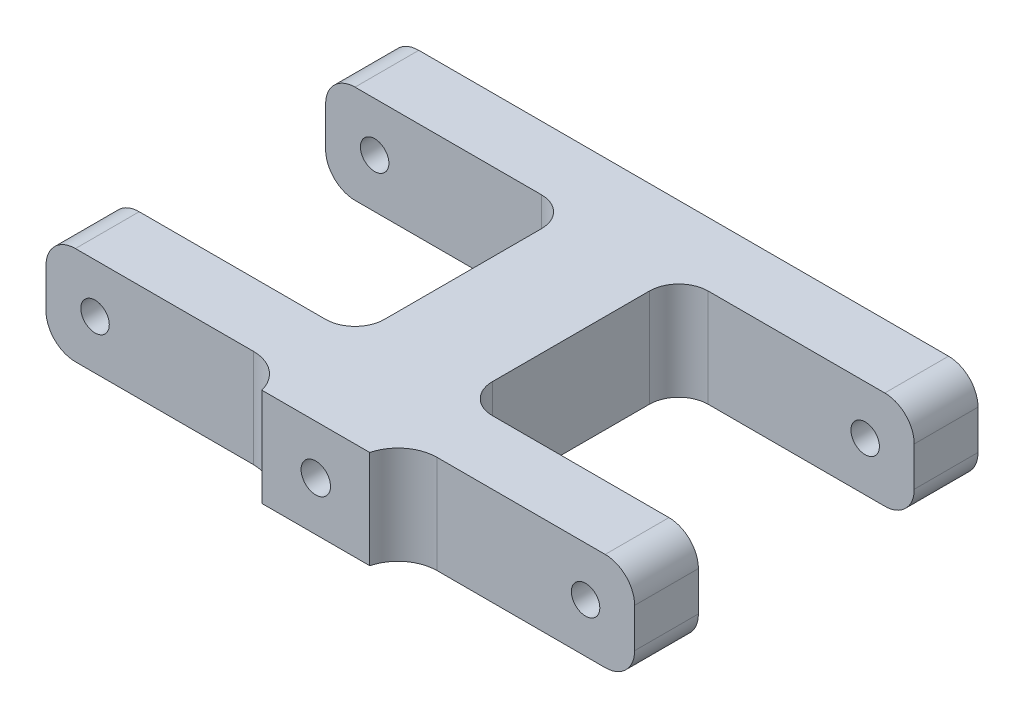
SolidWorks part; units mm, degrees
ref_plane "Front" through (0, 0, 0) normal (0, 0, 1) x (1, 0, 0)
ref_plane "Top" through (0, 0, 0) normal (0, 1, 0) x (1, 0, 0)
ref_plane "Right" through (0, 0, 0) normal (1, 0, 0) x (0, 0, -1)
sketch "Sketch1" plane through (0, 0, 0) normal (0, 1, 0) x (1, 0, 0)
  line L1 (0, 0) -> (60, 0)
  line L2 (0, 0) -> (0, -35)
  line L3 (0, -35) -> (60, -35)
  line L4 (60, 0) -> (60, -35)
  dimension "D1" = 35
  dimension "D2" = 60
extrude "Boss-Extrude1" add sketch "Sketch1" along normal blind 10
sketch "Sketch2" plane through (60, 0, 0) normal (1, 0, 0) x (0, 0, -1)
  line L0 (-35, 10) -> (0, 10) construction
  line L1 (-28.5, 10) -> (-6.5, 10)
  line L2 (-28.5, 10) -> (-28.5, 0)
  line L3 (-28.5, 0) -> (-6.5, 0)
  line L4 (-6.5, 10) -> (-6.5, 0)
  line L5 (-35, 0) -> (0, 0) construction
  line L6 (-35, 10) -> (-35, 0) construction
  line L7 (0, 10) -> (0, 0) construction
  dimension "D1" = 6.5
  dimension "D2" = 6.5
extrude "Cut-Extrude1" cut sketch "Sketch2" against normal blind 24
sketch "Sketch3" plane through (0, 0, 0) normal (-1, 0, 0) x (0, 0, 1)
  line L0 (0, 10) -> (35, 10) construction
  line L1 (6.5, 10) -> (28.5, 10)
  line L2 (6.5, 10) -> (6.5, 0)
  line L3 (6.5, 0) -> (28.5, 0)
  line L4 (28.5, 10) -> (28.5, 0)
  line L5 (0, 0) -> (35, 0) construction
  line L6 (35, 10) -> (35, 0) construction
  line L7 (0, 10) -> (0, 0) construction
  dimension "D1" = 6.5
  dimension "D2" = 6.5
extrude "Cut-Extrude2" cut sketch "Sketch3" against normal blind 25
sketch "Sketch5" plane through (0, 0, 35) normal (0, 0, 1) x (1, 0, 0)
  line L0 (0, 10) -> (60, 10) construction
  line L1 (0, 10) -> (0, 0) construction
  circle A0 centre (5, 5) radius 1.45
  circle A1 centre (55, 5) radius 1.45
  dimension "D1" = 2.9
  dimension "D2" = 5
  dimension "D3" = 5
  dimension "D4" = 2
extrude "Cut-Extrude4" cut sketch "Sketch5" against normal through all
fillet "Fillet1" radius 3 8 edges at (0, 0, 31.75) (0, 10, 31.75) (0, 0, 3.25) (0, 10, 3.25) (60, 10, 3.25) (60, 0, 3.25) (60, 0, 31.75) (60, 10, 31.75)
fillet "Fillet2" radius 3 4 edges at (36, 5, 28.5) (36, 5, 6.5) (25, 5, 28.5) (25, 5, 6.5)
sketch "Sketch7" plane through (0, 0, 35) normal (0, 0, 1) x (1, 0, 0)
  line L0 (3, 10) -> (57, 10) construction
  line L1 (25, 10) -> (36, 10)
  line L2 (25, 10) -> (25, 0)
  line L3 (25, 0) -> (36, 0)
  line L4 (36, 10) -> (36, 0)
  line L5 (3, 0) -> (57, 0) construction
  line L6 (60, 7) -> (60, 3) construction
  line L7 (0, 7) -> (0, 3) construction
  dimension "D1" = 24
  dimension "D2" = 25
extrude "Boss-Extrude2" add sketch "Sketch7" along normal blind 3
sketch "Sketch6" plane through (0, 0, 35) normal (0, 0, 1) x (1, 0, 0)
  line L0 (3, 0) -> (25, 0) construction
  line L2 (0, 7) -> (0, 3) construction
  circle A0 centre (30.5, 5) radius 1.5
  dimension "D1" = 3
  dimension "D2" = 5
  dimension "D3" = 30.5
extrude "Cut-Extrude5" cut sketch "Sketch6" against normal blind 15 and the other way blind 3
fillet "Fillet3" radius 4 2 edges at (36, 5, 35) (25, 5, 35)
